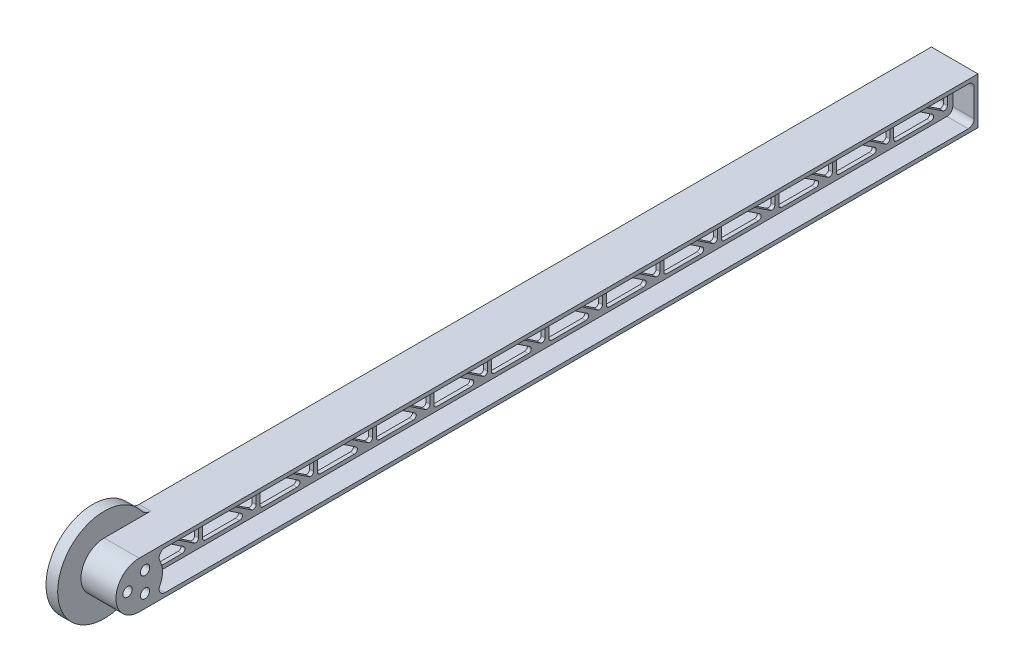
SolidWorks part; units mm, degrees
material "6061 Alloy"
ref_plane "Front Plane" through (0, 0, 0) normal (0, 0, 1) x (1, 0, 0)
ref_plane "Top Plane" through (0, 0, 0) normal (0, 1, 0) x (1, 0, 0)
ref_plane "Right Plane" through (0, 0, 0) normal (1, 0, 0) x (0, 0, -1)
sketch "Sketch1" plane through (0, 0, 0) normal (1, 0, 0) x (0, 0, -1)
  line L0 (-6.35, 0) -> (0, 0) construction
  line L1 (0, 0) -> (3.175, 5.4993) construction
  line L2 (0, 0) -> (3.175, -5.4993) construction
  line L3 (0, 12.7) -> (457.2, 12.7)
  line L4 (0, -12.7) -> (457.2, -12.7)
  line L5 (457.2, 12.7) -> (457.2, -12.7)
  circle A0 centre (3.175, 5.4993) radius 2.5527
  circle A1 centre (-6.35, 0) radius 2.5527
  circle A2 centre (3.175, -5.4993) radius 2.5527
  arc A3 (0, -12.7) -> (0, 12.7) centre (0, 0) cw
  dimension "D1" = 5.1054
  dimension "D5" = 12.7
  dimension "D2" = 6.35
  dimension "D3" = 120
  dimension "D4" = 120
  dimension "D6" = 457.2
extrude "Boss-Extrude1" add sketch "Sketch1" along normal mid plane 25.4
sketch "Sketch3" plane through (-12.7, 0, 0) normal (-1, 0, 0) x (0, 0, 1)
  circle A0 centre (0, 0) radius 25.4
  dimension "D1" = 50.8
extrude "Boss-Extrude2" add sketch "Sketch3" against normal blind 6.35
sketch "Sketch4" plane through (-6.35, 0, 0) normal (1, 0, 0) x (0, 0, -1)
  circle A0 centre (3.175, 5.4993) radius 2.5527 construction
  circle A1 centre (3.175, -5.4993) radius 2.5527 construction
  circle A2 centre (-6.35, 0) radius 2.5527 construction
  circle A3 centre (3.175, 5.4993) radius 2.5527
  circle A4 centre (3.175, -5.4993) radius 2.5527
  circle A5 centre (-6.35, 0) radius 2.5527
extrude "Cut-Extrude1" cut sketch "Sketch4" against normal through all
fillet "Fillet1" radius 6.35 2 edges at (-9.525, -12.7, -21.997) (-9.525, 12.7, -21.997)
sketch "Sketch5" plane through (12.7, 0, 0) normal (1, 0, 0) x (0, 0, -1)
  line L0 (457.2, 12.7) -> (455.0833, 12.7)
  line L1 (457.2, 12.7) -> (0, 12.7) construction
  line L2 (457.2, -12.7) -> (455.0833, -12.7)
  line L3 (0, -12.7) -> (457.2, -12.7) construction
  line L4 (455.0833, -12.7) -> (455.0833, 12.7)
  line L5 (0, 12.7) -> (0, 10.5833)
  line L6 (0, -12.7) -> (0, -10.5833)
  line L7 (0, 10.5833) -> (455.0833, 10.5833)
  line L8 (0, -10.5833) -> (455.0833, -10.5833)
  line L9 (426.7315, 8.4658) -> (452.1315, 8.4658)
  line L10 (448.3156, -8.4665) -> (452.1315, -8.4666)
  line L12 (12.7, 0) -> (12.7, 10.5833)
  line L13 (12.7, 0) -> (12.7, -10.5833)
  line L14 (12.7, 0) -> (14.8166, 0) construction
  line L15 (14.8166, 0) -> (14.8166, 8.4658)
  line L16 (14.8166, 0) -> (14.8166, -8.4582)
  line L17 (14.8166, 8.4658) -> (426.7315, 8.4658) construction
  line L18 (448.3156, -8.4665) -> (14.8166, -8.4582) construction
  line L19 (14.8166, -8.4582) -> (40.2166, -8.4587)
  line L20 (14.8166, 8.4658) -> (40.2166, -8.4587)
  line L21 (27.5166, 0.0036) -> (28.6902, 1.765) construction
  line L22 (28.6902, 1.765) -> (18.6337, 8.4658)
  line L23 (18.6337, 8.4658) -> (44.0337, 8.4658)
  line L24 (44.0337, 8.4658) -> (44.0337, -8.4588)
  line L25 (44.0337, -8.4588) -> (28.6902, 1.765)
  line L26 (44.0337, -8.4588) -> (46.1503, -8.4588) construction
  line L27 (46.1503, -8.4588) -> (46.1503, 8.4658)
  line L28 (46.1503, -8.4588) -> (71.5503, -8.4593)
  line L29 (71.5503, -8.4593) -> (46.1503, 8.4658)
  line L30 (58.8503, 0.0033) -> (60.0239, 1.7646) construction
  line L31 (60.0239, 1.7646) -> (49.9673, 8.4658)
  line L32 (49.9673, 8.4658) -> (75.3673, 8.4658)
  line L33 (75.3673, 8.4658) -> (75.3673, -8.4594)
  line L34 (75.3673, -8.4594) -> (60.0239, 1.7646)
  line L35 (75.3673, 8.4658) -> (77.4839, 8.4658)
  line L36 (77.4839, 8.4658) -> (77.4839, -8.4594)
  line L37 (77.4839, -8.4594) -> (102.8839, -8.4599)
  line L38 (77.4839, 8.4658) -> (102.8839, -8.4599)
  line L39 (90.1839, 0.003) -> (91.3576, 1.7644) construction
  line L40 (91.3576, 1.7644) -> (81.3009, 8.4658)
  line L41 (81.3009, 8.4658) -> (106.7009, 8.4658)
  line L42 (106.7009, 8.4658) -> (106.7009, -8.46)
  line L43 (106.7009, -8.46) -> (91.3576, 1.7644)
  line L44 (106.7009, 8.4658) -> (108.8175, 8.4658)
  line L45 (108.8175, 8.4658) -> (108.8175, -8.46)
  line L46 (108.8175, -8.46) -> (134.2175, -8.4605)
  line L47 (108.8175, 8.4658) -> (134.2175, -8.4605)
  line L48 (121.5175, 0.0027) -> (122.928, 2.1192) construction
  line L49 (122.928, 2.1192) -> (113.4041, 8.4658)
  line L50 (113.4041, 8.4658) -> (138.8041, 8.4658)
  line L51 (138.8041, 8.4658) -> (138.8041, -8.4606)
  line L52 (138.8041, -8.4606) -> (122.928, 2.1192)
  line L53 (138.8041, 8.4658) -> (140.9207, 8.4658)
  line L54 (140.9207, 8.4658) -> (140.9207, -8.4606)
  line L55 (140.9207, -8.4606) -> (166.3207, -8.4611)
  line L56 (166.3207, -8.4611) -> (140.9207, 8.4658)
  line L57 (153.6207, 0.0024) -> (154.7945, 1.7637) construction
  line L58 (154.7945, 1.7637) -> (144.7375, 8.4658)
  line L59 (144.7375, 8.4658) -> (170.1375, 8.4658)
  line L60 (170.1375, 8.4658) -> (170.1375, -8.4612)
  line L61 (170.1375, -8.4612) -> (154.7945, 1.7637)
  line L62 (170.1375, 8.4658) -> (172.254, 8.4658)
  line L63 (172.254, 8.4658) -> (172.254, -8.4612)
  line L64 (172.254, -8.4612) -> (197.654, -8.4617)
  line L65 (197.654, -8.4617) -> (172.254, 8.4658)
  line L66 (184.954, 0.0021) -> (186.1278, 1.7633) construction
  line L67 (186.1278, 1.7633) -> (176.0707, 8.4658)
  line L68 (176.0707, 8.4658) -> (201.4707, 8.4658)
  line L69 (201.4707, 8.4658) -> (201.4707, -8.4618)
  line L70 (201.4707, -8.4618) -> (186.1278, 1.7633)
  line L71 (201.4707, 8.4658) -> (203.5872, 8.4658)
  line L72 (203.5872, 8.4658) -> (203.5872, -8.4618)
  line L73 (203.5872, -8.4618) -> (228.9872, -8.4623)
  line L74 (203.5872, 8.4658) -> (228.9872, -8.4623)
  line L75 (216.2872, 0.0018) -> (217.4611, 1.763) construction
  line L76 (217.4611, 1.763) -> (207.4038, 8.4658)
  line L77 (207.4038, 8.4658) -> (232.8038, 8.4658)
  line L78 (232.8038, 8.4658) -> (232.8038, -8.4624)
  line L79 (232.8038, -8.4624) -> (217.4611, 1.763)
  line L80 (232.8038, 8.4658) -> (234.9196, 8.4658)
  line L81 (234.9196, 8.4658) -> (234.9196, -8.4624)
  line L82 (234.9196, -8.4624) -> (260.3196, -8.4629)
  line L83 (234.9196, 8.4658) -> (260.3196, -8.4629)
  line L84 (260.3196, -8.4629) -> (260.3492, -8.4364)
  line L85 (247.6196, 0.0015) -> (248.7934, 1.7627) construction
  line L86 (248.7934, 1.7627) -> (238.736, 8.4658)
  line L87 (238.736, 8.4658) -> (264.136, 8.4658)
  line L88 (264.136, 8.4658) -> (264.136, -8.463)
  line L89 (264.136, -8.463) -> (248.7934, 1.7627)
  line L90 (264.136, 8.4658) -> (266.2526, 8.4658)
  line L91 (266.2526, 8.4658) -> (266.2526, -8.463)
  line L92 (266.2526, -8.463) -> (291.6526, -8.4635)
  line L93 (291.6526, -8.4635) -> (266.2526, 8.4658)
  line L94 (278.9526, 0.0012) -> (280.1265, 1.7624) construction
  line L95 (280.1265, 1.7624) -> (270.069, 8.4658)
  line L96 (270.069, 8.4658) -> (295.469, 8.4658)
  line L97 (295.469, 8.4658) -> (295.469, -8.4636)
  line L98 (295.469, -8.4636) -> (280.1265, 1.7624)
  line L99 (295.469, 8.4658) -> (297.5856, 8.4658)
  line L100 (297.5856, 8.4658) -> (297.5856, -8.4636)
  line L101 (297.5856, -8.4636) -> (322.9856, -8.4641)
  line L102 (297.5856, 8.4658) -> (322.9856, -8.4641)
  line L103 (310.2856, 0.0009) -> (311.4595, 1.7621) construction
  line L104 (311.4595, 1.7621) -> (301.4018, 8.4658)
  line L105 (301.4018, 8.4658) -> (326.8018, 8.4658)
  line L106 (326.8018, 8.4658) -> (326.8018, -8.4642)
  line L107 (326.8018, -8.4642) -> (311.4595, 1.7621)
  line L108 (326.8018, 8.4658) -> (328.9184, 8.4658)
  line L109 (328.9184, 8.4658) -> (328.9184, -8.4642)
  line L110 (328.9184, -8.4642) -> (354.3184, -8.4647)
  line L111 (328.9184, 8.4658) -> (354.3184, -8.4647)
  line L112 (341.6184, 0.0006) -> (342.7923, 1.7617) construction
  line L113 (342.7923, 1.7617) -> (332.7345, 8.4658)
  line L114 (332.7345, 8.4658) -> (358.1345, 8.4658)
  line L115 (358.1345, 8.4658) -> (358.1345, -8.4648)
  line L116 (358.1345, -8.4648) -> (342.7923, 1.7617)
  line L117 (358.1345, 8.4658) -> (360.2511, 8.4658)
  line L118 (360.2511, 8.4658) -> (360.2511, -8.4648)
  line L119 (360.2511, -8.4648) -> (385.6511, -8.4653)
  line L120 (385.6511, -8.4653) -> (360.2511, 8.4658)
  line L121 (372.9511, 0.0003) -> (374.1251, 1.7614) construction
  line L122 (374.1251, 1.7614) -> (364.0672, 8.4658)
  line L123 (364.0672, 8.4658) -> (389.4672, 8.4658)
  line L124 (389.4672, 8.4658) -> (389.4672, -8.4654)
  line L125 (389.4672, -8.4654) -> (374.1251, 1.7614)
  line L126 (389.4672, 8.4658) -> (391.5838, 8.4658)
  line L127 (391.5838, 8.4658) -> (389.4672, 8.4658)
  line L128 (391.5838, 8.4658) -> (391.5838, -8.4654)
  line L129 (391.5838, -8.4654) -> (416.9838, -8.4659)
  line L130 (391.5838, 8.4658) -> (416.9838, -8.4659)
  line L131 (404.2838, 0) -> (405.4578, 1.7611) construction
  line L132 (405.4578, 1.7611) -> (395.3998, 8.4658)
  line L133 (395.3998, 8.4658) -> (420.7998, 8.4658)
  line L134 (420.7998, 8.4658) -> (420.7998, -8.466)
  line L135 (420.7998, -8.466) -> (405.4578, 1.7611)
  line L136 (420.7998, 8.4658) -> (422.9156, 8.4658)
  line L137 (422.9156, 8.4658) -> (422.9156, -8.466)
  line L138 (422.9156, -8.466) -> (448.3156, -8.4665)
  line L139 (422.9156, 8.4658) -> (448.3156, -8.4665)
  line L140 (435.6156, -0.0003) -> (436.7896, 1.7608) construction
  line L141 (436.7896, 1.7608) -> (426.7315, 8.4658)
  line L143 (452.1315, 8.4658) -> (452.1315, -8.4666)
  line L144 (452.1315, -8.4666) -> (436.7896, 1.7608)
  circle A0 centre (0, 0) radius 12.7
  dimension "D3" = 25.4
  dimension "D1" = 2.1167
  dimension "D2" = 2.1167
  dimension "D4" = 2.1167
  dimension "D5" = 2.1167
  dimension "D9" = 2.1166
  dimension "D10" = 8.4658
  dimension "D11" = 8.4582
  dimension "D13" = 25.4
  dimension "D14" = 2.1166
  dimension "D15" = 25.4
  dimension "D16" = 2.1166
  dimension "D17" = 25.4
  dimension "D18" = 2.1166
  dimension "D19" = 25.4
  dimension "D20" = 2.1166
  dimension "D21" = 25.4
  dimension "D22" = 2.1167
  dimension "D23" = 25.4
  dimension "D24" = 2.1166
  dimension "D25" = 25.4
  dimension "D26" = 2.1166
  dimension "D27" = 25.4
  dimension "D28" = 2.1166
  dimension "D29" = 25.4
  dimension "D30" = 2.1166
  dimension "D31" = 25.4
  dimension "D32" = 2.1166
  dimension "D33" = 25.4
  dimension "D34" = 2.1166
  dimension "D35" = 25.4
  dimension "D36" = 2.1166
  dimension "D37" = 25.4
  dimension "D38" = 2.1166
  dimension "D39" = 25.4
  dimension "D40" = 2.1158
  dimension "D41" = 25.4
  dimension "D42" = 2.1166
  dimension "D43" = 25.4
  dimension "D44" = 2.1166
  dimension "D45" = 25.4
  dimension "D46" = 2.1166
  dimension "D47" = 25.4
  dimension "D48" = 2.1166
  dimension "D49" = 25.4
  dimension "D50" = 2.1166
  dimension "D51" = 25.4
  dimension "D52" = 2.1166
  dimension "D53" = 25.4
  dimension "D54" = 2.1166
  dimension "D55" = 25.4
  dimension "D56" = 2.1166
  dimension "D57" = 25.4
  dimension "D58" = 2.1166
  dimension "D59" = 25.4
  dimension "D60" = 2.1166
  dimension "D61" = 25.4
  dimension "D62" = 2.1166
  dimension "D63" = 25.4
  dimension "D64" = 2.1158
  dimension "D65" = 25.4
  dimension "D66" = 2.1166
  dimension "D67" = 25.4
extrude "Cut-Extrude2" cut sketch "Sketch5" against normal through all contours L20 L15 L16 L18 | L25 L24 L17 L22 | L18 L29 L27 | L34 L33 L17 L31 | L38 L36 L18 | L43 L42 L17 L40 | L47 L45 L18 | L52 L51 L17 L49 | L18 L56 L54 | L61 L60 L17 L58 | L18 L65 L63 | L70 L69 L17 L67 | L74 L72 L18 | L79 L78 L17 L76 | L83 L81 L18 | L89 L88 L17 L86 | L18 L93 L91 | L98 L97 L17 L95 | L102 L100 L18 | L107 L106 L17 L104 | L111 L109 L18 | L116 L115 L17 L113 | L18 L120 L118 | L125 L124 L17 L122 | L130 L128 L18 | L135 L134 L17 L132 | L139 L137 L18 | L144 L143 L9 L141 region at (12.7, 2.8219, -412.3331) region at (12.7, -2.8222, -431.3822) region at (12.7, 2.8217, -443.6648) region at (12.7, -2.817, -23.2832) region at (12.7, 2.8243, -35.567) region at (12.7, -2.8174, -54.6169) region at (12.7, -2.8178, -85.9505) region at (12.7, 2.8241, -66.9006) region at (12.7, -2.8182, -117.2842) region at (12.7, 2.8239, -98.2343) region at (12.7, -2.8186, -149.3874) region at (12.7, 2.8237, -130.3375) region at (12.7, -2.819, -180.7207) region at (12.7, 2.8235, -161.6708) region at (12.7, -2.8194, -212.0539) region at (12.7, 2.8233, -193.004) region at (12.7, -2.8198, -243.3863) region at (12.7, 2.8231, -224.3371) region at (12.7, -2.8202, -274.7193) region at (12.7, 2.8229, -255.6694) region at (12.7, -2.8206, -306.0522) region at (12.7, 2.8227, -287.0023) region at (12.7, -2.821, -337.3851) region at (12.7, 2.8225, -318.3352) region at (12.7, -2.8214, -368.7178) region at (12.7, 2.8223, -349.6679) region at (12.7, -2.8218, -400.0504) region at (12.7, 2.8221, -381.0005)
extrude "Cut-Extrude3" cut sketch "Sketch5<5>" against normal blind 11.6417 contours L12 L13 L8 L4 L7 L130 L129 L128 L124 L125 L122 L123 L93 L92 L91 L88 L89 L86 L87 L83 L82 L81 L78 L79 L76 L77 L74 L73 L72 L69 L70 L67 L68 L56 L55 L54 | A0 L12 L7 | A0 L8 L13 region at (12.7, -0.0031, -234.2608) region at (12.7, -8.0702, -11.0896) region at (12.7, 8.0702, -11.0896)
sketch "Sketch5<5>" plane through (12.7, 0, 0) normal (1, 0, 0) x (0, 0, -1) same geometry as "Sketch5"
sketch "Sketch7" plane through (-12.7, 0, 0) normal (-1, 0, 0) x (0, 0, 1)
  line L0 (-25.4, 12.7) -> (0, 12.7)
  line L1 (-25.4, -12.7) -> (0, -12.7)
  line L2 (0, 12.7) -> (0, 10.5834)
  line L3 (0, -12.7) -> (0, -10.5834)
  line L4 (-457.2, 12.7) -> (-457.2, 10.5834)
  line L5 (-457.2, -12.7) -> (-457.2, 12.7) construction
  line L6 (-457.2, -12.7) -> (-457.2, -10.5834)
  line L7 (0, 10.5834) -> (-457.2, 10.5834)
  line L8 (-457.2, -10.5834) -> (0, -10.5834)
  line L9 (-457.2, 12.7) -> (-455.0834, 12.7)
  line L10 (-457.2, 12.7) -> (-25.4, 12.7) construction
  line L11 (-457.2, -12.7) -> (-455.0834, -12.7)
  line L12 (-25.4, -12.7) -> (-457.2, -12.7) construction
  line L13 (-455.0834, 12.7) -> (-455.0834, -12.7)
  circle A0 centre (0, 0) radius 12.7
  dimension "D1" = 25.4
  dimension "D2" = 2.1166
  dimension "D3" = 2.1166
  dimension "D4" = 2.1166
  dimension "D5" = 2.1166
  dimension "D6" = 2.1166
  dimension "D7" = 2.1166
extrude "Cut-Extrude4" cut sketch "Sketch7" against normal blind 11.6417 contours A0 L7 L13 L8 region at (-12.7, 0, -233.0471)
fillet "Fillet2" radius 3.175 8 edges at (-6.8792, -10.5834, -455.0834) (6.8792, -10.5833, -455.0833) (-6.8792, 10.5834, -455.0834) (6.8792, 10.5833, -455.0833) (-6.8792, -10.5834, -7.0201) (6.8792, -10.5833, -7.0202) (-6.8792, 10.5834, -7.0201) (6.8792, 10.5833, -7.0202)
fillet "Fillet3" radius 1.5875 84 edges at (0, -8.4588, -46.1503) (0, 8.4658, -46.1503) (0, -8.4593, -71.5503) (0, -8.4594, -75.3673) (0, 8.4658, -49.9673) (0, 8.4658, -75.3673) (0, 8.4658, -77.4839) (0, -8.4599, -102.8839) (0, -8.4594, -77.4839) (0, -8.46, -106.7009) (0, 8.4658, -81.3009) (0, 8.4658, -106.7009) (0, 8.4658, -108.8175) (0, -8.4605, -134.2175) (0, -8.46, -108.8175) (0, -8.4606, -138.8041) (0, 8.4658, -113.4041) (0, 8.4658, -138.8041) (0, -8.4612, -172.254) (0, 8.4658, -172.254) (0, -8.4617, -197.654) (0, -8.4618, -201.4707) (0, 8.4658, -176.0707) (0, 8.4658, -201.4707) (0, 8.4658, -203.5872) (0, -8.4623, -228.9872) (0, -8.4618, -203.5872) (0, -8.4624, -232.8038) (0, 8.4658, -207.4038) (0, 8.4658, -232.8038) (0, 8.4658, -234.9196) (0, -8.4629, -260.3196) (0, -8.4624, -234.9196) (0, -8.463, -264.136) (0, 8.4658, -238.736) (0, 8.4658, -264.136) (0, -8.4648, -360.2511) (0, 8.4658, -360.2511) (0, -8.4653, -385.6511) (0, -8.4654, -389.4672) (0, 8.4658, -364.0672) (0, 8.4658, -389.4672) (0, 8.4658, -391.5838) (0, -8.4659, -416.9838) (0, -8.4654, -391.5838) (0, -8.466, -420.7998) (0, 8.4658, -395.3998) (0, 8.4658, -420.7998) (0, 8.4658, -422.9156) (0, -8.4665, -448.3156) (0, -8.466, -422.9156) (0, -8.4666, -452.1315) (0, 8.4658, -426.7315) (0, 8.4658, -452.1315) (0, -8.4648, -358.1345) (0, 8.4658, -332.7345) (0, 8.4658, -358.1345) (0, 8.4658, -328.9184) (0, -8.4647, -354.3184) (0, -8.4642, -328.9184) (0, -8.4642, -326.8018) (0, 8.4658, -301.4018) (0, 8.4658, -326.8018) (0, 8.4658, -297.5856) (0, -8.4641, -322.9856) (0, -8.4636, -297.5856) (0, -8.4636, -295.469) (0, 8.4658, -270.069) (0, 8.4658, -295.469) (0, -8.463, -266.2526) (0, 8.4658, -266.2526) (0, -8.4635, -291.6526) (0, -8.4612, -170.1375) (0, 8.4658, -144.7375) (0, 8.4658, -170.1375) (0, -8.4606, -140.9207) (0, 8.4658, -140.9207) (0, -8.4611, -166.3207) (0, -8.4588, -44.0337) (0, 8.4658, -18.6337) (0, 8.4658, -44.0337) (0, 8.4658, -14.8166) (0, -8.4587, -40.2166) (0, -8.4582, -14.8166)
